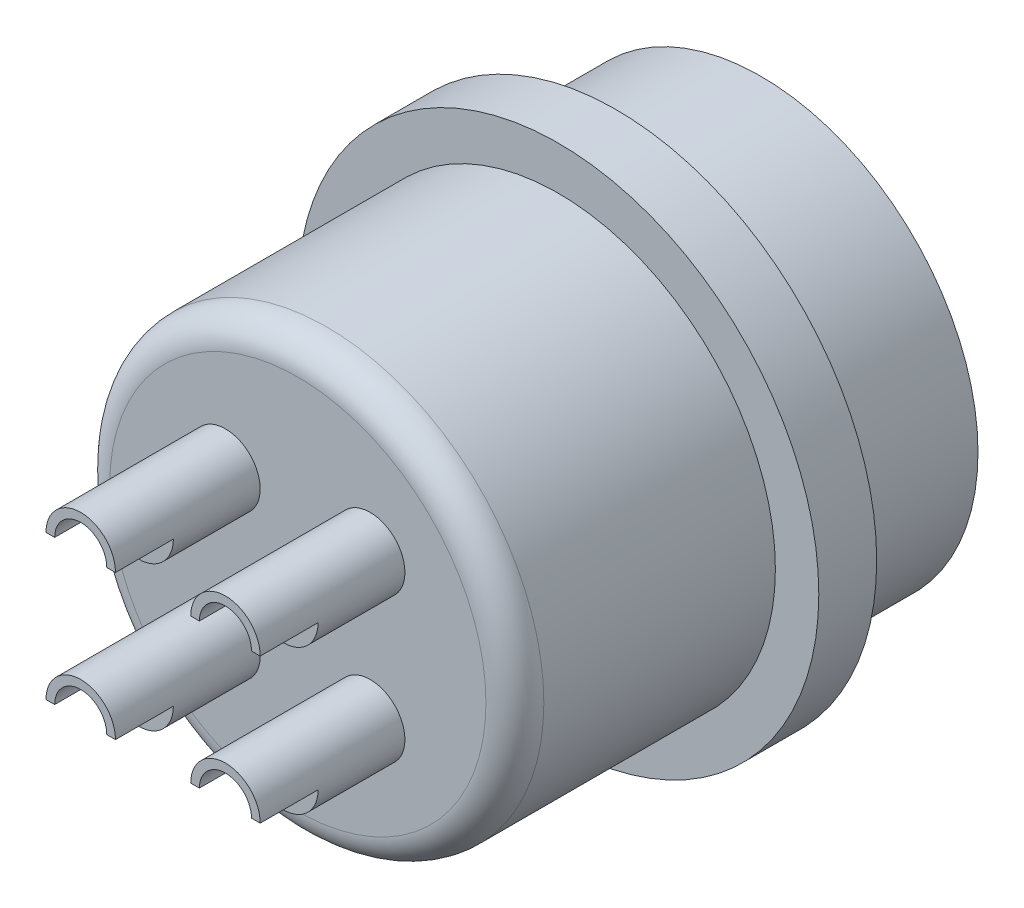
SolidWorks part; units mm, degrees
ref_plane "Спереди" through (0, 0, 0) normal (0, 0, 1) x (1, 0, 0)
ref_plane "Сверху" through (0, 0, 0) normal (0, 1, 0) x (1, 0, 0)
ref_plane "Справа" through (0, 0, 0) normal (1, 0, 0) x (0, 0, -1)
sketch "Эскиз1" plane through (0, 0, 0) normal (0, 0, 1) x (1, 0, 0)
  circle A0 centre (0, 0) radius 7.5
  dimension "D1" = 15
extrude "Бобышка-Вытянуть1" add sketch "Эскиз1" along normal blind 5
sketch "Эскиз2" plane through (0, 0, 5) normal (0, 0, 1) x (1, 0, 0)
  circle A0 centre (0, 0) radius 9
  dimension "D1" = 18
extrude "Бобышка-Вытянуть2" add sketch "Эскиз2" along normal blind 2
sketch "Эскиз3" plane through (0, 0, 7) normal (0, 0, 1) x (1, 0, 0)
  circle A0 centre (0, 0) radius 7.5
  dimension "D1" = 15
extrude "Бобышка-Вытянуть3" add sketch "Эскиз3" along normal blind 9
sketch "Эскиз5" plane through (0, 0, 0) normal (0, 0, -1) x (-1, 0, 0)
  line L0 (0, 0) -> (0, -10.7973) construction
  arc A0 (0.997, -6.4231) -> (-0.997, -6.4231) centre (0, 0) ccw
  arc A1 (0.997, -6.4231) -> (-0.997, -6.4231) centre (0, -6.5) ccw
  dimension "D1" = 13
  dimension "D2" = 2
extrude "Вырез-Вытянуть1" cut sketch "Эскиз5" against normal blind 10
sketch "Эскиз4" plane through (0, 0, 16) normal (0, 0, 1) x (1, 0, 0)
  line L0 (0, 0) -> (0, 3.3016) construction
  line L1 (0, 0) -> (-2.6551, 0) construction
  line L3 (-3.7, 3.7) -> (3.7, 3.7) construction
  line L4 (-3.7, 3.7) -> (-3.7, -3.7) construction
  line L5 (-3.7, -3.7) -> (3.7, -3.7) construction
  line L6 (3.7, 3.7) -> (3.7, -3.7) construction
  circle A0 centre (-2.5, 2.5) radius 1.2
  circle A1 centre (-2.5, -2.5) radius 1.2
  circle A2 centre (2.5, -2.5) radius 1.2
  circle A3 centre (2.5, 2.5) radius 1.2
  dimension "D3" = 2.4
  dimension "D4" = 2.4
  dimension "D5" = 2.4
  dimension "D6" = 2.4
  dimension "D1" = 7.4
  dimension "D2" = 7.4
extrude "Бобышка-Вытянуть4" add sketch "Эскиз4" along normal blind 5 and the other way blind 14
sketch "Эскиз6" plane through (0, 0, 21) normal (0, 0, 1) x (1, 0, 0)
  line L0 (-4.0656, 2.5) -> (-3.4, 2.5)
  line L1 (-1.0227, 2.5) -> (-1.8133, 1.1102)
  line L2 (-1.8133, 1.1102) -> (-3.3049, 1.1102)
  line L3 (-3.3049, 1.1102) -> (-4.0656, 2.5)
  line L4 (-1.6, 2.5) -> (-1.0227, 2.5)
  line L5 (0, 0) -> (0, 1.6965) construction
  line L6 (0, 0) -> (1.6386, 0) construction
  line L7 (1.6, 2.5) -> (1.0227, 2.5)
  line L8 (4.0656, 2.5) -> (3.4, 2.5)
  line L9 (3.3049, 1.1102) -> (4.0656, 2.5)
  line L10 (1.8133, 1.1102) -> (3.3049, 1.1102)
  line L11 (1.0227, 2.5) -> (1.8133, 1.1102)
  line L12 (4.0656, -2.5) -> (3.4, -2.5)
  line L13 (3.3049, -3.8898) -> (4.0656, -2.5)
  line L14 (-1.0227, -2.5) -> (-1.8133, -3.8898)
  line L15 (-3.3049, -3.8898) -> (-4.0656, -2.5)
  line L16 (1.0227, -2.5) -> (1.8133, -3.8898)
  line L17 (1.8133, -3.8898) -> (3.3049, -3.8898)
  line L18 (-4.0656, -2.5) -> (-3.4, -2.5)
  line L19 (-1.6, -2.5) -> (-1.0227, -2.5)
  line L20 (1.6, -2.5) -> (1.0227, -2.5)
  line L21 (-1.8133, -3.8898) -> (-3.3049, -3.8898)
  arc A0 (-1.6, 2.5) -> (-3.4, 2.5) centre (-2.5, 2.5) ccw
  circle A1 centre (-2.5, 2.5) radius 1.2 construction
  arc A2 (1.6, 2.5) -> (3.4, 2.5) centre (2.5, 2.5) cw
  arc A3 (1.6, -2.5) -> (3.4, -2.5) centre (2.5, -2.5) cw
  arc A4 (-1.6, -2.5) -> (-3.4, -2.5) centre (-2.5, -2.5) ccw
  dimension "D1" = 0.3
extrude "Вырез-Вытянуть2" cut sketch "Эскиз6" against normal blind 2
fillet "Скругление1" radius 1 4 edges at (3.7, -2.5, 2) (-1.3, -2.5, 2) (-1.3, 2.5, 2) (3.7, 2.5, 2)
fillet "Скругление2" radius 1 1 edges at (7.5, 0, 16)
sketch "0_0_Point" plane through (0, 0, 16) normal (0, 0, 1) x (1, 0, 0)
  point P0 (-2.4908, -2.76)
other "0_0" parameters "Diameter"=2, "StubLength"=2
ref_axis "Axis1" through (-2.4908, -2.76, 26) along (0, 0, -1)
sketch "2_0_Point" plane through (0, 0, 16) normal (0, 0, 1) x (1, 0, 0)
  point P0 (2.5224, -2.8523)
sketch "1_0_Point" plane through (0, 0, 16) normal (0, 0, 1) x (1, 0, 0)
  point P0 (2.7531, 2.3174)
sketch "3_0_Point" plane through (0, 0, 16) normal (0, 0, 1) x (1, 0, 0)
  point P0 (-2.4016, 2.2312)
other "1_0" parameters "Diameter"=2, "StubLength"=2
ref_axis "Axis2" through (2.7531, 2.3174, 26) along (0, 0, -1)
other "2_0" parameters "Diameter"=2, "StubLength"=2
ref_axis "Axis3" through (2.5224, -2.8523, 26) along (0, 0, -1)
other "3_0" parameters "Diameter"=2, "StubLength"=2
ref_axis "Axis4" through (-2.4016, 2.2312, 26) along (0, 0, -1)
ref_plane "Plane1" through (0, 0, 28) normal (0, 0, 1) x (1, 0, 0)
sketch "EwCable_Point" plane through (0, 0, 28) normal (0, 0, 1) x (1, 0, 0)
  point P0 (0, 0)
other "EwCable" parameters "Diameter"=2, "StubLength"=2
ref_axis "Axis5" through (0, 0, 38) along (0, 0, -1)
